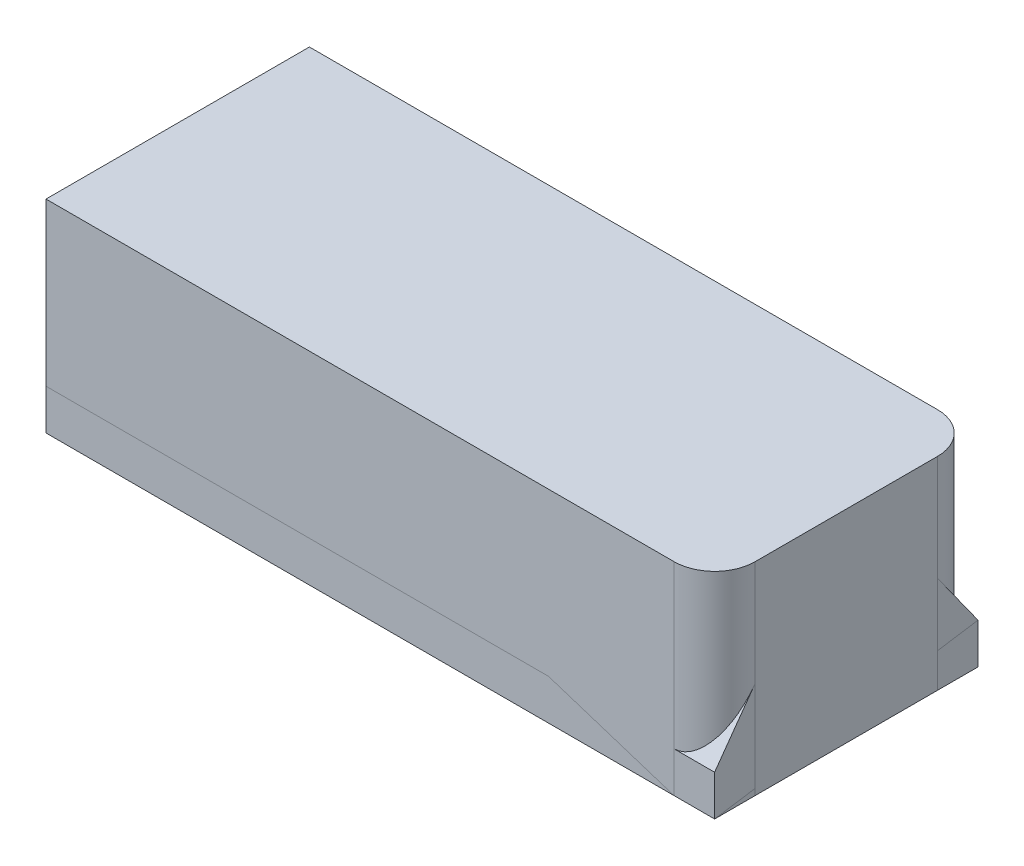
SolidWorks part; units mm, degrees
ref_plane "Front Plane" through (0, 0, 0) normal (0, 0, 1) x (1, 0, 0)
ref_plane "Top Plane" through (0, 0, 0) normal (0, 1, 0) x (1, 0, 0)
ref_plane "Right Plane" through (0, 0, 0) normal (1, 0, 0) x (0, 0, -1)
sketch "Sketch1" plane through (0, 0, 0) normal (0, 1, 0) x (1, 0, 0)
  line L0 (0, 0) -> (0, 20.6375)
  line L1 (0, 20.6375) -> (49.2125, 20.6375)
  line L2 (52.3875, 17.4625) -> (52.3875, 3.175)
  line L3 (49.2125, 0) -> (0, 0)
  arc A0 (49.2125, 20.6375) -> (52.3875, 17.4625) centre (49.2125, 17.4625) cw
  arc A1 (52.3875, 3.175) -> (49.2125, 0) centre (49.2125, 3.175) cw
  point P9 (46.0375, 0)
  point P10 (46.0375, 20.6375)
  point P11 (0, 0)
  dimension "D4" = 3.175
  dimension "D1" = 20.6375
  dimension "D2" = 46.0375
  dimension "D3" = 6.35
sketch "Sketch2" plane through (0, 0, 0) normal (0, 0, 1) x (1, 0, 0)
  line L0 (0, 0) -> (0, 3.175)
  line L1 (0, 3.175) -> (1.5875, 3.175)
  line L2 (1.5875, 3.175) -> (1.5875, 15.875)
  line L3 (1.5875, 15.875) -> (4.7625, 15.875)
  line L4 (4.7625, 15.875) -> (4.7625, 3.175)
  line L5 (4.7625, 3.175) -> (9.525, 3.175)
  line L6 (9.525, 3.175) -> (9.525, 15.875)
  line L7 (9.525, 15.875) -> (12.7, 15.875)
  line L8 (12.7, 15.875) -> (12.7, 3.175)
  line L9 (12.7, 3.175) -> (52.3875, 3.175)
  line L10 (52.3875, 3.175) -> (52.3875, 0)
  line L11 (52.3875, 0) -> (0, 0)
  dimension "D1" = 3.175
  dimension "D2" = 1.5875
  dimension "D3" = 12.7
  dimension "D4" = 3.175
  dimension "D5" = 4.7625
  dimension "D6" = 52.3875
sketch "Sketch3" plane through (0, 0, 0) normal (1, 0, 0) x (0, 0, -1)
  line L0 (0, 0) -> (0, 3.175)
  line L1 (0, 3.175) -> (8.3828, 14.8802)
  line L2 (12.2547, 14.8802) -> (20.6375, 3.175)
  line L3 (20.6375, 3.175) -> (20.6375, 0)
  line L4 (20.6375, 0) -> (0, 0)
  arc A0 (8.3828, 14.8802) -> (12.2547, 14.8802) centre (10.3187, 13.4937) cw
  circle A1 centre (10.3187, 13.4937) radius 0.7938
  dimension "D3" = 2.3813
  dimension "D5" = 1.5875
  dimension "D1" = 3.175
  dimension "D2" = 10.3187
  dimension "D4" = 20.6375
  dimension "D6" = 54.391
extrude "Boss-Extrude1" add sketch "Sketch1" along normal blind 15.875
extrude "Boss-Extrude2" add sketch "Sketch2" against normal blind 20.6375 separate body
extrude "Boss-Extrude3" add sketch "Sketch3" along normal blind 52.3875 separate body
equation "\"D6@Sketch2\"= \"D2@Sketch1\" + \"D3@Sketch1\""
equation "\"D4@Sketch3\"= \"D1@Sketch1\""
